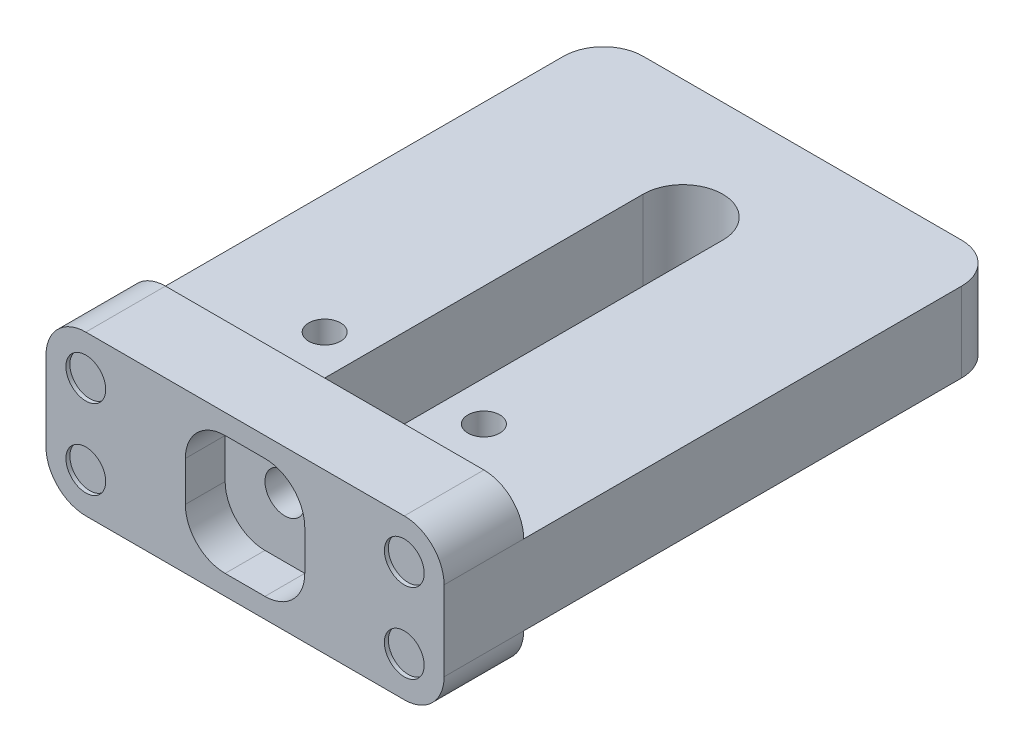
SolidWorks part; units mm, degrees
ref_plane "正面" through (0, 0, 0) normal (0, 0, 1) x (1, 0, 0)
ref_plane "平面" through (0, 0, 0) normal (0, 1, 0) x (1, 0, 0)
ref_plane "右側面" through (0, 0, 0) normal (1, 0, 0) x (0, 0, -1)
sketch "ｽｹｯﾁ1" plane through (0, 0, 0) normal (0, 1, 0) x (1, 0, 0)
  line L0 (0, -60) -> (0, 60) construction
  line L1 (-50, -60) -> (50, -60)
  line L2 (-50, -60) -> (-50, 60)
  line L3 (-50, 60) -> (50, 60)
  line L4 (50, -60) -> (50, 60)
  line L5 (-50, -60) -> (50, 60) construction
  line L6 (-50, 60) -> (50, -60) construction
  circle A0 centre (-20, -40) radius 4
  circle A1 centre (20, -40) radius 4
  point P0 (0, 0)
  dimension "D1" = 8
  dimension "D2" = 40
  dimension "D4" = 100
  dimension "D5" = 120
  dimension "D6" = 20
extrude "ﾎﾞｽ - 押し出し1" add sketch "ｽｹｯﾁ1" along normal blind 20
sketch "ｽｹｯﾁ4" plane through (0, 0, 60) normal (0, 0, 1) x (1, 0, 0)
  line L0 (-50, 20) -> (-50, 0) construction
  line L1 (-50, -10) -> (50, -10)
  line L2 (-50, -10) -> (-50, 30)
  line L3 (-50, 30) -> (50, 30)
  line L4 (50, -10) -> (50, 30)
  line L5 (50, 20) -> (50, 0) construction
  point P4 (49.978, 20.0781)
  point P7 (-50, 10)
  point P8 (-50, 10)
  point P11 (50, 10)
  point P12 (50, 10)
  dimension "D1" = 40
extrude "ﾎﾞｽ - 押し出し2" add sketch "ｽｹｯﾁ4" along normal blind 20
sketch "ｽｹｯﾁ5" plane through (0, 0, 80) normal (0, 0, 1) x (1, 0, 0)
  line L0 (0, 30) -> (0, -10) construction
  line L1 (50, 30) -> (-50, 30) construction
  line L2 (-50, -10) -> (50, -10) construction
  line L3 (-50, 10) -> (50, 10) construction
  line L4 (-50, 30) -> (-50, -10) construction
  line L5 (50, -10) -> (50, 30) construction
  line L7 (-15, -5) -> (15, -5)
  line L8 (-15, -5) -> (-15, 25)
  line L9 (-15, 25) -> (15, 25)
  line L10 (15, -5) -> (15, 25)
  line L11 (-15, -5) -> (15, 25) construction
  line L12 (-15, 25) -> (15, -5) construction
  point P12 (0, 10)
  dimension "D1" = 30
  dimension "D2" = 30
extrude "ｶｯﾄ - 押し出し1" cut sketch "ｽｹｯﾁ5" against normal blind 10
sketch "ｽｹｯﾁ7" plane through (0, 0, 70) normal (0, 0, 1) x (1, 0, 0)
  line L0 (15, -5) -> (15, 25) construction
  line L5 (15, 25) -> (-15, 25) construction
  circle A0 centre (0, 10) radius 5
  point P4 (0, 25)
  point P10 (15, 10)
  dimension "D1" = 10
extrude "ｶｯﾄ - 押し出し3" cut sketch "ｽｹｯﾁ7" against normal offset from surface (110 mm away) 20 up to face at (0, 10, -60)
sketch "ｽｹｯﾁ8" plane through (0, 0, 80) normal (0, 0, 1) x (1, 0, 0)
  line L0 (0, 30) -> (0, -10) construction
  line L1 (50, 30) -> (-50, 30) construction
  line L2 (-50, -10) -> (50, -10) construction
  line L3 (-50, 10) -> (50, 10) construction
  line L4 (-50, 30) -> (-50, -10) construction
  line L5 (50, -10) -> (50, 30) construction
  circle A0 centre (-40, 20) radius 5
  circle A1 centre (40, 20) radius 5
  circle A2 centre (40, 0) radius 5
  circle A3 centre (-40, 0) radius 5
  dimension "D1" = 10
  dimension "D3" = 10
  dimension "D2" = 10
extrude "ｶｯﾄ - 押し出し4" cut sketch "ｽｹｯﾁ8" against normal blind 1
sketch "ｽｹｯﾁ9" plane through (0, 20, 0) normal (0, 1, 0) x (1, 0, 0)
  line L0 (50, -60) -> (-50, -60) construction
  line L1 (-10, -60) -> (10, -60)
  line L2 (-10, -60) -> (-10, 40)
  line L3 (-10, 40) -> (10, 40)
  line L4 (10, -60) -> (10, 40)
  line L5 (50, 60) -> (-50, 60) construction
  line L6 (-50, -60) -> (50, -60) construction
  point P10 (0, -60)
  point P11 (0, -60)
  dimension "D1" = 20
  dimension "D2" = 20
extrude "ｶｯﾄ - 押し出し6" cut sketch "ｽｹｯﾁ9" against normal through all
fillet "ﾌｨﾚｯﾄ5" radius 10 4 edges at (15, 25, 75) (15, -5, 75) (-15, -5, 75) (-15, 25, 75)
fillet "ﾌｨﾚｯﾄ2" radius 10 2 edges at (50, 10, -60) (-50, 10, -60)
fillet "ﾌｨﾚｯﾄ1" radius 10 4 edges at (50, 30, 70) (50, -10, 70) (-50, -10, 70) (-50, 30, 70)
fillet "ﾌｨﾚｯﾄ9" 2 edges at (-10, 10, -40) (10, 10, -40) type full round first side face at (-10, 10, 10) second side face at (10, 10, 10) middle face at (0, 10, -40)
